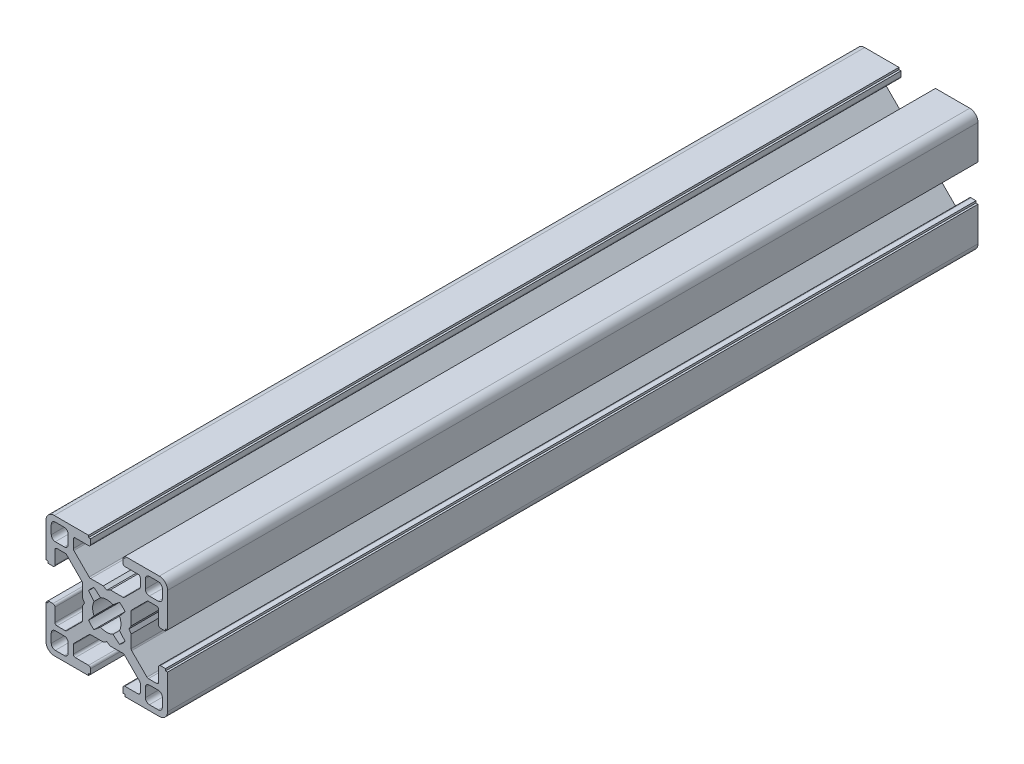
SolidWorks part; units mm, degrees
ref_plane "Front Plane" through (0, 0, 0) normal (0, 0, 1) x (1, 0, 0)
ref_plane "Top Plane" through (0, 0, 0) normal (0, 1, 0) x (1, 0, 0)
ref_plane "Right Plane" through (0, 0, 0) normal (1, 0, 0) x (0, 0, -1)
sketch "Sketch1" plane through (0, 0, 0) normal (0, 0, 1) x (1, 0, 0)
  line L0 (-15, 0) -> (15, 0) construction
  line L1 (0, -15) -> (0, 15) construction
  line L2 (-4.5, 15) -> (4.5, 15) construction
  line L3 (-4, -15) -> (4, -15) construction
  line L4 (-4.5, 15) -> (-4.5, 14.5)
  line L5 (-4.5, 14.5) -> (-4, 14.5)
  line L6 (-4, 14.5) -> (-4, 13.29)
  line L7 (-4.5, 12.79) -> (-7.7675, 12.79)
  line L8 (-8.2675, 12.29) -> (-8.2675, 10.2707)
  line L9 (-8.1211, 9.9171) -> (-4.3504, 6.1464)
  line L10 (-3.9968, 6) -> (0, 6)
  line L11 (0, 0) -> (-15, 15) construction
  line L12 (-4.5, 15) -> (-12.968, 15)
  line L14 (-12.705, 9.5135) -> (-10.5135, 9.5135)
  line L15 (-13.705, 10.5135) -> (-13.705, 12.705)
  line L16 (-12.705, 13.705) -> (-10.5135, 13.705)
  line L17 (-9.5135, 10.5135) -> (-9.5135, 12.705)
  line L18 (-13.705, 9.5135) -> (-9.5135, 13.705) construction
  line L19 (-13.705, 13.705) -> (-9.5135, 9.5135) construction
  line L20 (-3.1568, 4.5038) -> (-1.5303, 3.1477) construction
  line L21 (-4.5038, 3.1568) -> (-3.1477, 1.5303) construction
  line L22 (-6, 3.9968) -> (-6, 0)
  line L23 (-9.9171, 8.1211) -> (-6.1464, 4.3504)
  line L24 (-15, 4.5) -> (-15, 12.968)
  line L25 (-12.29, 8.2675) -> (-10.2707, 8.2675)
  line L26 (-12.79, 4.5) -> (-12.79, 7.7675)
  line L27 (-14.5, 4) -> (-13.29, 4)
  line L28 (-14.5, 4.5) -> (-14.5, 4)
  line L29 (-15, 4.5) -> (-14.5, 4.5)
  circle A0 centre (0, 0) radius 3.5
  arc A1 (-12.968, 15) -> (-15, 12.968) centre (-12.968, 12.968) ccw
  circle A2 centre (0, 0) radius 5.5 construction
  arc A3 (-10.5135, 9.5135) -> (-9.5135, 10.5135) centre (-10.5135, 10.5135) ccw
  arc A4 (-13.705, 12.705) -> (-12.705, 13.705) centre (-12.705, 12.705) cw
  arc A5 (-10.5135, 13.705) -> (-9.5135, 12.705) centre (-10.5135, 12.705) cw
  arc A6 (-12.705, 9.5135) -> (-13.705, 10.5135) centre (-12.705, 10.5135) cw
  arc A7 (-12.79, 4.5) -> (-13.29, 4) centre (-13.29, 4.5) cw
  arc A8 (-12.29, 8.2675) -> (-12.79, 7.7675) centre (-12.29, 7.7675) ccw
  arc A9 (-9.9171, 8.1211) -> (-10.2707, 8.2675) centre (-10.2707, 7.7675) ccw
  arc A10 (-6, 3.9968) -> (-6.1464, 4.3504) centre (-6.5, 3.9968) ccw
  arc A11 (-4.3504, 6.1464) -> (-3.9968, 6) centre (-3.9968, 6.5) ccw
  arc A12 (-4, 13.29) -> (-4.5, 12.79) centre (-4.5, 13.29) cw
  arc A13 (-7.7675, 12.79) -> (-8.2675, 12.29) centre (-7.7675, 12.29) ccw
  arc A14 (-8.2675, 10.2707) -> (-8.1211, 9.9171) centre (-7.7675, 10.2707) ccw
  point P4 (0, 0)
  point P8 (0, 0)
  point P13 (0, 15)
  point P15 (0, -15)
  point P16 (0, 6)
  point P23 (-11.6092, 11.6093)
  point P26 (0, 6)
  point P62 (-12.79, 4)
  point P65 (-12.79, 8.2675)
  point P68 (-10.0636, 8.2675)
  point P71 (-6, 4.2039)
  point P74 (-4.2039, 6)
  point P77 (-4, 12.79)
  point P80 (-8.2675, 12.79)
  point P83 (-8.2675, 10.0636)
  dimension "Center Hole Diameter" = 7
  dimension "D11" = 2.032
  dimension "D9" = 11
  dimension "D13" = 1
  dimension "D14" = 0.5
  dimension "Rail Height" = 30
  dimension "Rail Width" = 30
  dimension "T-Slot Width" = 8
  dimension "T-Slot Depth" = 9
  dimension "D1" = 9
  dimension "D2" = 45
  dimension "D3" = 8
  dimension "D4" = 2.21
  dimension "D5" = 16.535
  dimension "D7" = 2.54
  dimension "D6" = 1.295
  dimension "D8" = 1.246
  dimension "D10" = 10.36
  dimension "D12" = 1.905
sketch "Sketch2" plane through (0, 0, 0) normal (1, 0, 0) x (0, 0, -1)
  line L0 (-76.2, 0) -> (76.2, 0) construction
  line L2 (0, -15) -> (0, 15) construction
  line L3 (0, -15) -> (0, 15) construction
  line L4 (-76.2, -15) -> (-76.2, 15) construction
  line L5 (76.2, -15) -> (76.2, 15) construction
  point P0 (-38.7, 0)
  point P3 (0, 0)
  point P4 (38.7, 0)
  point P12 (-76.2, 0)
  point P14 (76.2, 0)
  dimension "Length" = 152.4
  dimension "D1" = 37.5
sketch "Sketch3" plane through (0, 0, 0) normal (0, 0, 1) x (1, 0, 0)
  line L0 (-4.5038, 3.1568) -> (-3.1477, 1.5303)
  line L1 (0, 3.5) -> (0, 5.5)
  line L2 (-5.5, 0) -> (-3.5, 0)
  line L7 (-6, 3.9968) -> (-6, 0) construction
  line L31 (-9.9171, 8.1211) -> (-6.1464, 4.3504) construction
  line L117 (-12.29, 8.2675) -> (-10.2707, 8.2675) construction
  line L118 (-12.79, 4.5) -> (-12.79, 7.7675) construction
  line L157 (-12.705, 9.5135) -> (-10.5135, 9.5135)
  line L158 (-9.5135, 10.5135) -> (-9.5135, 12.705)
  line L163 (-10.5135, 13.705) -> (-12.705, 13.705)
  line L164 (-13.705, 12.705) -> (-13.705, 10.5135)
  line L165 (-12.705, 9.5135) -> (-10.5135, 9.5135)
  line L166 (-9.5135, 10.5135) -> (-9.5135, 12.705)
  line L167 (-10.5135, 13.705) -> (-12.705, 13.705)
  line L168 (-13.705, 12.705) -> (-13.705, 10.5135)
  line L169 (-14.5, 4) -> (-13.29, 4) construction
  line L170 (-14.5, 4.5) -> (-14.5, 4) construction
  line L171 (-15, 4.5) -> (-14.5, 4.5) construction
  line L172 (-15, 4.5) -> (-15, 12.968) construction
  line L173 (-4.5, 15) -> (-12.968, 15) construction
  line L174 (-4.5, 15) -> (-4.5, 14.5) construction
  line L175 (-4.5, 14.5) -> (-4, 14.5) construction
  line L176 (-4, 14.5) -> (-4, 13.29) construction
  line L177 (-4.5, 12.79) -> (-7.7675, 12.79) construction
  line L178 (-8.2675, 12.29) -> (-8.2675, 10.2707) construction
  line L179 (-8.1211, 9.9171) -> (-4.3504, 6.1464) construction
  line L180 (-3.9968, 6) -> (0, 6) construction
  line L181 (-6, 3.9968) -> (-6, 0.866)
  line L182 (-9.9171, 8.1211) -> (-6.1464, 4.3504)
  line L183 (-12.29, 8.2675) -> (-10.2707, 8.2675)
  line L184 (-12.79, 4.5) -> (-12.79, 7.7675)
  line L185 (-14.5, 4) -> (-13.29, 4)
  line L186 (-14.5, 4.5) -> (-14.5, 4)
  line L187 (-15, 4.5) -> (-14.5, 4.5)
  line L188 (-15, 4.5) -> (-15, 12.968)
  line L189 (-4.5, 15) -> (-12.968, 15)
  line L190 (-4.5, 15) -> (-4.5, 14.5)
  line L191 (-4.5, 14.5) -> (-4, 14.5)
  line L192 (-4, 14.5) -> (-4, 13.29)
  line L193 (-4.5, 12.79) -> (-7.7675, 12.79)
  line L194 (-8.2675, 12.29) -> (-8.2675, 10.2707)
  line L195 (-8.1211, 9.9171) -> (-4.3504, 6.1464)
  line L196 (-3.9968, 6) -> (-0.866, 6)
  line L197 (-0.866, 6) -> (0, 5.5)
  line L198 (0, -15) -> (0, 15) construction
  line L199 (0, 0) -> (-15, 15) construction
  line L200 (0, 0) -> (-15, 15) construction
  line L201 (-3.1568, 4.5038) -> (-1.5303, 3.1477) construction
  line L202 (-3.1568, 4.5038) -> (-1.5303, 3.1477)
  line L203 (-6, 0.866) -> (-5.5, 0)
  line L204 (-15, 0) -> (15, 0) construction
  line L205 (-15, 0) -> (15, 0) construction
  line L206 (0, -15) -> (0, 15) construction
  arc A0 (-3.5, 0) -> (-3.1477, 1.5303) centre (0, 0) cw
  arc A10 (-6, 3.9968) -> (-6.1464, 4.3504) centre (-6.5, 3.9968) ccw construction
  circle A16 centre (0, 0) radius 3.5
  arc A18 (0, 3.5) -> (-1.5303, 3.1477) centre (0, 0) ccw
  arc A20 (-9.9171, 8.1211) -> (-10.2707, 8.2675) centre (-10.2707, 7.7675) ccw construction
  arc A22 (-12.29, 8.2675) -> (-12.79, 7.7675) centre (-12.29, 7.7675) ccw construction
  arc A28 (-13.29, 4) -> (-12.79, 4.5) centre (-13.29, 4.5) ccw construction
  arc A29 (-10.5135, 9.5135) -> (-9.5135, 10.5135) centre (-10.5135, 10.5135) ccw
  arc A30 (-9.5135, 12.705) -> (-10.5135, 13.705) centre (-10.5135, 12.705) ccw
  arc A31 (-12.705, 13.705) -> (-13.705, 12.705) centre (-12.705, 12.705) ccw
  arc A32 (-13.705, 10.5135) -> (-12.705, 9.5135) centre (-12.705, 10.5135) ccw
  arc A33 (-10.5135, 9.5135) -> (-9.5135, 10.5135) centre (-10.5135, 10.5135) ccw
  arc A34 (-9.5135, 12.705) -> (-10.5135, 13.705) centre (-10.5135, 12.705) ccw
  arc A35 (-12.705, 13.705) -> (-13.705, 12.705) centre (-12.705, 12.705) ccw
  arc A36 (-13.705, 10.5135) -> (-12.705, 9.5135) centre (-12.705, 10.5135) ccw
  arc A37 (-12.968, 15) -> (-15, 12.968) centre (-12.968, 12.968) ccw construction
  arc A38 (-4.5, 12.79) -> (-4, 13.29) centre (-4.5, 13.29) ccw construction
  arc A39 (-7.7675, 12.79) -> (-8.2675, 12.29) centre (-7.7675, 12.29) ccw construction
  arc A40 (-8.2675, 10.2707) -> (-8.1211, 9.9171) centre (-7.7675, 10.2707) ccw construction
  arc A41 (-4.3504, 6.1464) -> (-3.9968, 6) centre (-3.9968, 6.5) ccw construction
  arc A42 (-6, 3.9968) -> (-6.1464, 4.3504) centre (-6.5, 3.9968) ccw
  arc A43 (-9.9171, 8.1211) -> (-10.2707, 8.2675) centre (-10.2707, 7.7675) ccw
  arc A44 (-12.29, 8.2675) -> (-12.79, 7.7675) centre (-12.29, 7.7675) ccw
  arc A45 (-13.29, 4) -> (-12.79, 4.5) centre (-13.29, 4.5) ccw
  arc A46 (-12.968, 15) -> (-15, 12.968) centre (-12.968, 12.968) ccw
  arc A47 (-4.5, 12.79) -> (-4, 13.29) centre (-4.5, 13.29) ccw
  arc A48 (-7.7675, 12.79) -> (-8.2675, 12.29) centre (-7.7675, 12.29) ccw
  arc A49 (-8.2675, 10.2707) -> (-8.1211, 9.9171) centre (-7.7675, 10.2707) ccw
  arc A50 (-4.3504, 6.1464) -> (-3.9968, 6) centre (-3.9968, 6.5) ccw
  circle A51 centre (0, 0) radius 5.5 construction
  arc A52 (-3.1568, 4.5038) -> (-4.5038, 3.1568) centre (0, 0) ccw
  dimension "D3" = 60
  dimension "D4" = 60
  dimension "D1" = 0
  dimension "D2" = 0
extrude "Boss-Extrude1" add sketch "Sketch3" along normal mid plane 200
pattern_circular "CirPattern1" count 4 over 360 about axis through (0, 0, 76.2) along (0, 0, -1) of "Boss-Extrude1"
ref_plane "Contact Plane1" through (15, 0, 0) normal (1, 0, 0) x (0, 0, -1)
ref_plane "Contact Plane2" through (0, -15, 0) normal (0, 1, 0) x (1, 0, 0)
ref_plane "Contact Plane3" through (-15, 0, 0) normal (1, 0, 0) x (0, 0, -1)
ref_plane "Contact Plane4" through (0, 15, 0) normal (0, 1, 0) x (1, 0, 0)
equation "\"D1@Sketch2\" = \"Rail Height@Sketch1\" * 1.25"
equation "\"D1@Sketch1\"=\"T-Slot Width@Sketch1\"+1mm"
equation "\"D3@Sketch1\"=\"T-Slot Width@Sketch1\""
equation "\"D1@Boss-Extrude1\"=\"Width\""
equation "\"Width\"= 200mm"
